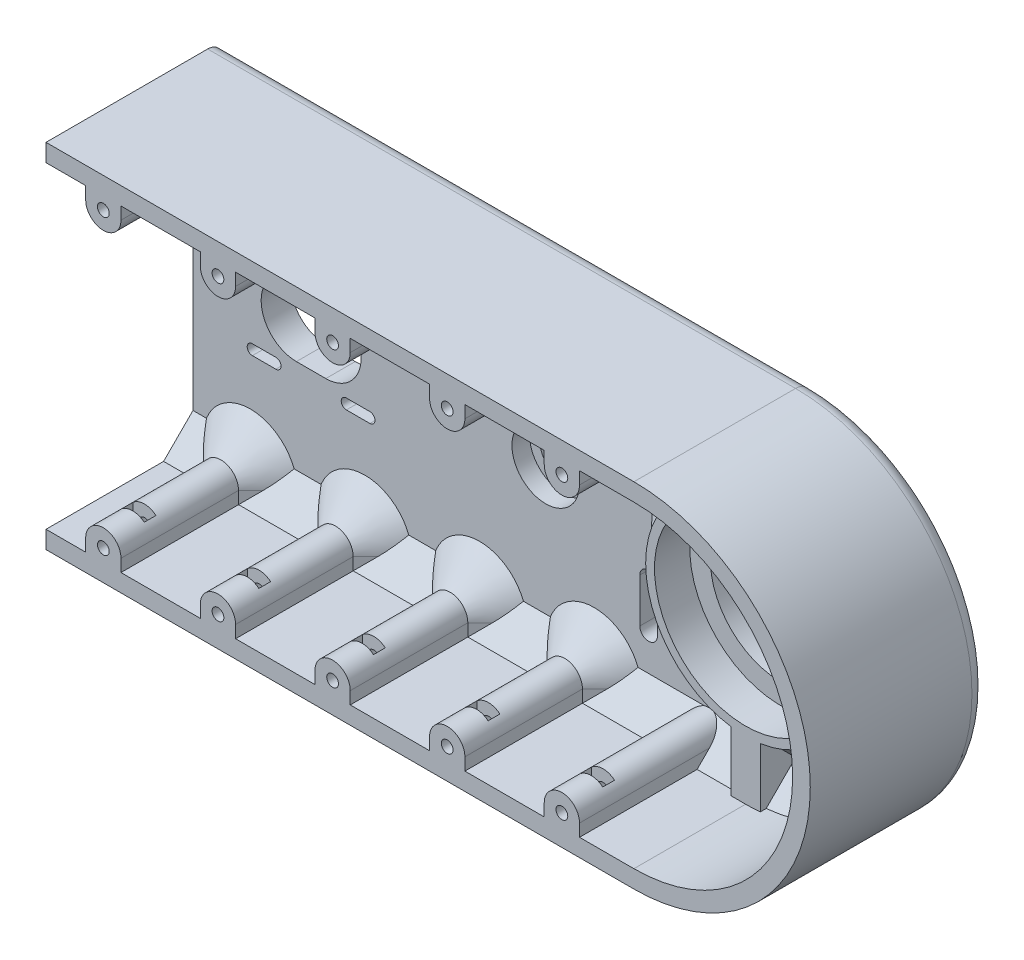
SolidWorks part; units mm, degrees
other "Marcação1"
sketch "Esboço6" plane through (60, -60, 0) normal (0.0064, -0.8941, -0.4477) x (-0.9984, -0.0306, 0.047)
sketch "Esboço8" plane through (60, -60, 0) normal (0.0064, -0.8941, -0.4477) x (-0.9984, -0.0306, 0.047)
sketch "Esboço13" plane through (60, -60, 0) normal (0.0064, -0.8941, -0.4477) x (-0.9984, -0.0306, 0.047)
sketch "Esboço15" plane through (60, -60, 0) normal (0.0064, -0.8941, -0.4477) x (-0.9984, -0.0306, 0.047)
ref_plane "Plano frontal" through (0, 0, 0) normal (0, 0, 1) x (1, 0, 0)
ref_plane "Plano superior" through (0, 0, 0) normal (0, 1, 0) x (1, 0, 0)
ref_plane "Plano direito" through (0, 0, 0) normal (1, 0, 0) x (0, 0, -1)
sketch "Esboço2" plane through (0, 0, 0) normal (0, 0, 1) x (1, 0, 0)
  line L0 (0, 60) -> (-200, 60)
  line L1 (-200, 60) -> (-200, -60)
  line L2 (-200, -60) -> (0, -60)
  circle A0 centre (0, 0) radius 19
  arc A1 (0, -60) -> (0, 60) centre (0, 0) ccw
  dimension "D1" = 38
  dimension "D2" = 120
  dimension "D3" = 200
extrude "Ressalto-extrusão1" add sketch "Esboço2" along normal blind 10
sketch "Esboço3" plane through (0, 0, 10) normal (0, 0, 1) x (1, 0, 0)
  circle A0 centre (0, 0) radius 24
  dimension "D1" = 48
extrude "Corte-extrusão1" cut sketch "Esboço3" against normal blind 7
sketch "Esboço4" plane through (0, 0, 10) normal (0, 0, 1) x (1, 0, 0)
  circle A0 centre (0, 0) radius 31
  circle A1 centre (0, 0) radius 34
  dimension "D1" = 62
  dimension "D2" = 68
extrude "Ressalto-extrusão2" add sketch "Esboço4" along normal blind 12
sketch "Esboço5" plane through (0, 0, 10) normal (0, 0, 1) x (1, 0, 0)
  line L0 (-200, 60) -> (0, 60)
  line L1 (-200, -60) -> (0, -60)
  line L2 (-200, 60) -> (-200, 54)
  line L3 (-200, 60) -> (-200, -60) construction
  line L4 (-200, -60) -> (-200, -54)
  line L5 (-200, 54) -> (0, 54)
  line L6 (-200, -54) -> (0, -54)
  arc A0 (0, -60) -> (0, 60) centre (0, 0) ccw
  arc A2 (0, -54) -> (0, 54) centre (0, 0) ccw
  dimension "D1" = 6
extrude "Ressalto-extrusão3" add sketch "Esboço5" along normal blind 50
sketch "Esboço7" plane through (0, 0, 0) normal (0, 0, -1) x (-1, 0, 0)
  line L0 (0, 60) -> (200, 60) construction
  line L1 (143.82, 15.99) -> (175.8, 15.99) construction
  line L2 (143.82, 15.99) -> (143.82, -15.99) construction
  line L3 (143.82, -15.99) -> (175.8, -15.99) construction
  line L4 (175.8, 15.99) -> (175.8, -15.99) construction
  line L5 (200, 60) -> (200, -60) construction
  line L6 (143.82, -15.99) -> (175.8, 15.99) construction
  line L7 (143.82, 15.99) -> (175.8, -15.99) construction
  line L8 (147.82, 15.99) -> (139.82, 15.99) construction
  line L9 (147.82, 14.24) -> (139.82, 14.24)
  line L10 (147.82, 17.74) -> (139.82, 17.74)
  line L11 (179.8, 17.74) -> (171.8, 17.74)
  line L12 (179.8, 14.24) -> (171.8, 14.24)
  line L13 (179.8, 15.99) -> (171.8, 15.99) construction
  line L14 (179.8, -17.74) -> (171.8, -17.74)
  line L15 (179.8, -14.24) -> (171.8, -14.24)
  line L16 (147.82, -14.24) -> (139.82, -14.24)
  line L17 (147.82, -17.74) -> (139.82, -17.74)
  line L18 (147.82, -15.99) -> (139.82, -15.99) construction
  line L19 (179.8, -15.99) -> (171.8, -15.99) construction
  line L20 (164.81, 0) -> (154.81, 0) construction
  line L21 (164.81, -12) -> (154.81, -12)
  line L22 (164.81, 12) -> (154.81, 12)
  arc A6 (147.82, 14.24) -> (147.82, 17.74) centre (147.82, 15.99) ccw
  arc A7 (139.82, 17.74) -> (139.82, 14.24) centre (139.82, 15.99) ccw
  arc A8 (179.8, 14.24) -> (179.8, 17.74) centre (179.8, 15.99) ccw
  arc A9 (171.8, 17.74) -> (171.8, 14.24) centre (171.8, 15.99) ccw
  arc A10 (171.8, -14.24) -> (171.8, -17.74) centre (171.8, -15.99) ccw
  arc A11 (179.8, -17.74) -> (179.8, -14.24) centre (179.8, -15.99) ccw
  arc A12 (147.82, -17.74) -> (147.82, -14.24) centre (147.82, -15.99) ccw
  arc A13 (139.82, -14.24) -> (139.82, -17.74) centre (139.82, -15.99) ccw
  arc A14 (164.81, -12) -> (164.81, 12) centre (164.81, 0) ccw
  arc A15 (154.81, 12) -> (154.81, -12) centre (154.81, 0) ccw
  point P10 (175.8, 0)
  point P17 (159.81, 0)
  point P19 (143.82, 15.99)
  point P24 (175.8, 15.99)
  point P33 (143.82, -15.99)
  point P38 (175.8, -15.99)
  dimension "D2" = 2
  dimension "D6" = 1.75
  dimension "D9" = 12
  dimension "D1" = 31.98
  dimension "D3" = 60
  dimension "D4" = 24.2
  dimension "D7" = 8
  dimension "D10" = 10
  dimension "D8" = 2
extrude "Corte-extrusão2" cut sketch "Esboço7" against normal up to surface (10 mm away) up to face at (34, 0, 10)
sketch "Esboço9" plane through (0, 0, 10) normal (0, 0, 1) x (1, 0, 0)
  line L0 (0, 0) -> (-200, 0) construction
  line L1 (-200, 54) -> (-200, -54) construction
  circle A0 centre (-80, 0) radius 11.5
  circle A1 centre (0, 0) radius 19 construction
  point P12 (-200, 0)
  dimension "D1" = 23
  dimension "D2" = 80
extrude "Corte-extrusão3" cut sketch "Esboço9" against normal blind 6 contours A0
sketch "Esboço10" plane through (0, 0, 4) normal (0, 0, 1) x (1, 0, 0)
  circle A0 centre (-80, 0) radius 8
  dimension "D1" = 16
extrude "Corte-extrusão4" cut sketch "Esboço10" against normal up to surface (4 mm away) up to face at (-175.8, -15.99, 0)
sketch "Esboço11" plane through (0, 0, 22) normal (0, 0, 1) x (1, 0, 0)
  line L0 (0, 34) -> (0, 60)
  line L1 (60, 0) -> (34, 0)
  line L2 (0, -34) -> (0, -60)
  circle A0 centre (0, 0) radius 34 construction
  circle A1 centre (0, 0) radius 34 construction
  arc A5 (0, -60) -> (0, 60) centre (0, 0) ccw construction
rib "Nervura1" sketch "Esboço11" sketch "Esboço11" thickness 10 extrusion direction normal to sketch draft on no parameters "D1"=10
sketch "Esboço12" plane through (0, 0, 10) normal (0, 0, 1) x (1, 0, 0)
  line L0 (-45, -16.5) -> (-45, -31.5) construction
  line L1 (-42, -16.5) -> (-42, -31.5)
  line L2 (-48, -16.5) -> (-48, -31.5)
  line L3 (-5, -54) -> (-200, -54) construction
  line L4 (0, 60) -> (-200, 60) construction
  line L5 (-200, 54) -> (-200, -54) construction
  arc A0 (-42, -16.5) -> (-48, -16.5) centre (-45, -16.5) ccw
  arc A1 (-48, -31.5) -> (-42, -31.5) centre (-45, -31.5) ccw
  circle A2 centre (-52, 20) radius 1.5
  circle A3 centre (-42.5, 20) radius 1.5
  point P2 (-45, -24)
  dimension "D1" = 3
  dimension "D5" = 3
  dimension "D6" = 3
  dimension "D7" = 9.5
  dimension "D8" = 40
  dimension "D9" = 148
  dimension "D2" = 15
  dimension "D3" = 30
  dimension "D4" = 45
extrude "Corte-extrusão5" cut sketch "Esboço12" against normal up to surface (10 mm away) up to face at (19, 0, 0)
sketch "Esboço14" plane through (0, 0, 10) normal (0, 0, 1) x (1, 0, 0)
  line L0 (-5, 49.8) -> (-200, 49.8) construction
  line L1 (-5, 54) -> (-5, 33.6303) construction
  line L2 (-200, 54) -> (-200, -54) construction
  line L3 (-200, 54) -> (0, 54) construction
  line L4 (-186.5, 49.8) -> (-186.5, 54.8)
  line L5 (-186.5, 54.8) -> (-174.5, 54.8)
  line L6 (-174.5, 54.8) -> (-174.5, 49.8)
  line L7 (-135.5, 54.8) -> (-135.5, 49.8)
  line L8 (-147.5, 54.8) -> (-135.5, 54.8)
  line L9 (-147.5, 49.8) -> (-147.5, 54.8)
  line L10 (-96.5, 54.8) -> (-96.5, 49.8)
  line L11 (-108.5, 54.8) -> (-96.5, 54.8)
  line L12 (-108.5, 49.8) -> (-108.5, 54.8)
  line L13 (-57.5, 54.8) -> (-57.5, 49.8)
  line L14 (-69.5, 54.8) -> (-57.5, 54.8)
  line L15 (-69.5, 49.8) -> (-69.5, 54.8)
  line L16 (-18.5, 54.8) -> (-18.5, 49.8)
  line L17 (-30.5, 54.8) -> (-18.5, 54.8)
  line L18 (-30.5, 49.8) -> (-30.5, 54.8)
  line L19 (33, 0) -> (-33, 0) construction
  line L20 (-30.5, -49.8) -> (-30.5, -54.8)
  line L21 (-30.5, -54.8) -> (-18.5, -54.8)
  line L22 (-18.5, -54.8) -> (-18.5, -49.8)
  line L23 (-69.5, -49.8) -> (-69.5, -54.8)
  line L24 (-69.5, -54.8) -> (-57.5, -54.8)
  line L25 (-57.5, -54.8) -> (-57.5, -49.8)
  line L26 (-108.5, -49.8) -> (-108.5, -54.8)
  line L27 (-108.5, -54.8) -> (-96.5, -54.8)
  line L28 (-96.5, -54.8) -> (-96.5, -49.8)
  line L29 (-147.5, -49.8) -> (-147.5, -54.8)
  line L30 (-147.5, -54.8) -> (-135.5, -54.8)
  line L31 (-135.5, -54.8) -> (-135.5, -49.8)
  line L32 (-174.5, -54.8) -> (-174.5, -49.8)
  line L33 (-186.5, -54.8) -> (-174.5, -54.8)
  line L34 (-186.5, -49.8) -> (-186.5, -54.8)
  arc A0 (-186.5, 49.8) -> (-174.5, 49.8) centre (-180.5, 49.8) ccw
  circle A1 centre (-180.5, 49.8) radius 2
  arc A2 (-147.5, 49.8) -> (-135.5, 49.8) centre (-141.5, 49.8) ccw
  circle A3 centre (-141.5, 49.8) radius 2
  arc A4 (-108.5, 49.8) -> (-96.5, 49.8) centre (-102.5, 49.8) ccw
  circle A5 centre (-102.5, 49.8) radius 2
  arc A6 (-69.5, 49.8) -> (-57.5, 49.8) centre (-63.5, 49.8) ccw
  circle A7 centre (-63.5, 49.8) radius 2
  arc A8 (-30.5, 49.8) -> (-18.5, 49.8) centre (-24.5, 49.8) ccw
  circle A9 centre (-24.5, 49.8) radius 2
  circle A10 centre (-24.5, -49.8) radius 2
  arc A11 (-30.5, -49.8) -> (-18.5, -49.8) centre (-24.5, -49.8) cw
  circle A12 centre (-63.5, -49.8) radius 2
  arc A13 (-69.5, -49.8) -> (-57.5, -49.8) centre (-63.5, -49.8) cw
  circle A14 centre (-102.5, -49.8) radius 2
  arc A15 (-108.5, -49.8) -> (-96.5, -49.8) centre (-102.5, -49.8) cw
  circle A16 centre (-141.5, -49.8) radius 2
  arc A17 (-147.5, -49.8) -> (-135.5, -49.8) centre (-141.5, -49.8) cw
  circle A18 centre (-180.5, -49.8) radius 2
  arc A19 (-186.5, -49.8) -> (-174.5, -49.8) centre (-180.5, -49.8) cw
  dimension "D2" = 19.5
  dimension "D3" = 4
  dimension "D4" = 12
  dimension "D1" = 4.2
  dimension "D5" = 5
  dimension "D6" = 5
extrude "Ressalto-extrusão5" add sketch "Esboço14" along normal up to surface (50 mm away) up to face at (-85.75, 0, 60)
ref_plane "Plano1" through (0, 0, 50) normal (0, 0, 1) x (1, 0, 0)
sketch "Esboço16" plane through (0, 0, 50) normal (0, 0, 1) x (1, 0, 0)
  line L0 (-186.5, 54) -> (-186.5, 49.8) construction
  line L1 (-184.4, 52.0517) -> (-184.4, 47.7483)
  line L4 (-176.6, 47.7483) -> (-176.6, 52.0517)
  line L5 (-176.6, 52.0517) -> (-180.5, 54.3033)
  line L6 (-180.5, 54.3033) -> (-184.4, 52.0517)
  line L7 (-184.4, 43.8) -> (-176.6, 43.8)
  line L8 (-176.6, 43.8) -> (-176.6, 47.7483)
  line L9 (-184.4, 43.8) -> (-184.4, 47.7483)
  line L10 (-145.4, 52.0517) -> (-145.4, 47.7483)
  line L11 (-182.5366, 46.4725) -> (-180.5866, 45.3467) [skipped]
  line L12 (-178.4634, 46.4725) -> (-176.5134, 47.5983) [skipped]
  line L13 (-141.5, 54.3033) -> (-145.4, 52.0517)
  line L14 (-137.6, 52.0517) -> (-141.5, 54.3033)
  line L15 (-137.6, 47.7483) -> (-137.6, 52.0517)
  line L16 (-137.6, 43.8) -> (-137.6, 47.7483)
  line L17 (-145.4, 43.8) -> (-145.4, 47.7483)
  line L18 (-145.4, 43.8) -> (-137.6, 43.8)
  line L19 (-106.4, 52.0517) -> (-106.4, 47.7483)
  line L20 (-102.5, 54.3033) -> (-106.4, 52.0517)
  line L21 (-98.6, 52.0517) -> (-102.5, 54.3033)
  line L22 (-98.6, 47.7483) -> (-98.6, 52.0517)
  line L23 (-98.6, 43.8) -> (-98.6, 47.7483)
  line L24 (-106.4, 43.8) -> (-106.4, 47.7483)
  line L25 (-106.4, 43.8) -> (-98.6, 43.8)
  line L26 (-67.4, 52.0517) -> (-67.4, 47.7483)
  line L27 (-63.5, 54.3033) -> (-67.4, 52.0517)
  line L28 (-59.6, 52.0517) -> (-63.5, 54.3033)
  line L29 (-59.6, 47.7483) -> (-59.6, 52.0517)
  line L30 (-59.6, 43.8) -> (-59.6, 47.7483)
  line L31 (-67.4, 43.8) -> (-67.4, 47.7483)
  line L32 (-67.4, 43.8) -> (-59.6, 43.8)
  line L33 (-28.4, 52.0517) -> (-28.4, 47.7483)
  line L34 (-24.5, 54.3033) -> (-28.4, 52.0517)
  line L35 (-20.6, 52.0517) -> (-24.5, 54.3033)
  line L36 (-20.6, 47.7483) -> (-20.6, 52.0517)
  line L37 (-20.6, 43.8) -> (-20.6, 47.7483)
  line L38 (-28.4, 43.8) -> (-28.4, 47.7483)
  line L39 (-28.4, 43.8) -> (-20.6, 43.8)
  line L40 (33, 0) -> (-33, 0) construction
  line L41 (-28.4, -43.8) -> (-20.6, -43.8)
  line L42 (-28.4, -43.8) -> (-28.4, -47.7483)
  line L43 (-20.6, -43.8) -> (-20.6, -47.7483)
  line L44 (-20.6, -47.7483) -> (-20.6, -52.0517)
  line L45 (-20.6, -52.0517) -> (-24.5, -54.3033)
  line L46 (-24.5, -54.3033) -> (-28.4, -52.0517)
  line L47 (-28.4, -52.0517) -> (-28.4, -47.7483)
  line L48 (-67.4, -43.8) -> (-59.6, -43.8)
  line L49 (-67.4, -43.8) -> (-67.4, -47.7483)
  line L50 (-59.6, -43.8) -> (-59.6, -47.7483)
  line L51 (-59.6, -47.7483) -> (-59.6, -52.0517)
  line L52 (-59.6, -52.0517) -> (-63.5, -54.3033)
  line L53 (-63.5, -54.3033) -> (-67.4, -52.0517)
  line L54 (-67.4, -52.0517) -> (-67.4, -47.7483)
  line L55 (-106.4, -43.8) -> (-98.6, -43.8)
  line L56 (-106.4, -43.8) -> (-106.4, -47.7483)
  line L57 (-98.6, -43.8) -> (-98.6, -47.7483)
  line L58 (-98.6, -47.7483) -> (-98.6, -52.0517)
  line L59 (-98.6, -52.0517) -> (-102.5, -54.3033)
  line L60 (-102.5, -54.3033) -> (-106.4, -52.0517)
  line L61 (-106.4, -52.0517) -> (-106.4, -47.7483)
  line L62 (-145.4, -43.8) -> (-137.6, -43.8)
  line L63 (-145.4, -43.8) -> (-145.4, -47.7483)
  line L64 (-137.6, -43.8) -> (-137.6, -47.7483)
  line L65 (-137.6, -47.7483) -> (-137.6, -52.0517)
  line L66 (-137.6, -52.0517) -> (-141.5, -54.3033)
  line L67 (-141.5, -54.3033) -> (-145.4, -52.0517)
  line L68 (-145.4, -52.0517) -> (-145.4, -47.7483)
  line L69 (-184.4, -43.8) -> (-184.4, -47.7483)
  line L70 (-176.6, -43.8) -> (-176.6, -47.7483)
  line L71 (-184.4, -43.8) -> (-176.6, -43.8)
  line L72 (-180.5, -54.3033) -> (-184.4, -52.0517)
  line L73 (-176.6, -52.0517) -> (-180.5, -54.3033)
  line L74 (-176.6, -47.7483) -> (-176.6, -52.0517)
  line L75 (-184.4, -52.0517) -> (-184.4, -47.7483)
  circle A0 centre (-180.5, 49.8) radius 3.9 construction
  circle A1 centre (-180.5, -49.8) radius 3.9 construction
  point P14 (-180.5, 43.8)
  point P84 (-180.5, -43.8)
  dimension "D1" = 7.8
  dimension "D2" = 10.5033
  dimension "D3" = 5
extrude "Corte-extrusão6" cut sketch "Esboço16" against normal blind 4
chamfer "Chanfro1" distance 10 angle 45 30 edges at (-63.5, 43.8, 10) (-102.5, 43.8, 10) (-141.5, 43.8, 10) (-180.5, 43.8, 10) (-193.25, 54, 10) (-44, 54, 10) (-83, 54, 10) (-122, 54, 10) (-161, 54, 10) (-180.5, -43.8, 10) (-141.5, -43.8, 10) (-102.5, -43.8, 10) (-63.5, -43.8, 10) (-44, -54, 10) (-83, -54, 10) (-193.25, -54, 10) (-161, -54, 10) (-122, -54, 10) (-11.75, 54, 10) (-11.75, -54, 10) (-5, 43.8152, 10) (-34, 0, 10) (-5, -43.8152, 10) (38.1838, -38.1838, 10) (24.0416, -24.0416, 10) (43.6992, -5, 10) (38.1838, 38.1838, 10) (43.6992, 5, 10) (24.0416, 24.0416, 10) (5, 43.6992, 10)
fillet "Filete1" radius 5 3 edges at (-100, -60, 0) (60, 0, 0) (-100, 60, 0)
